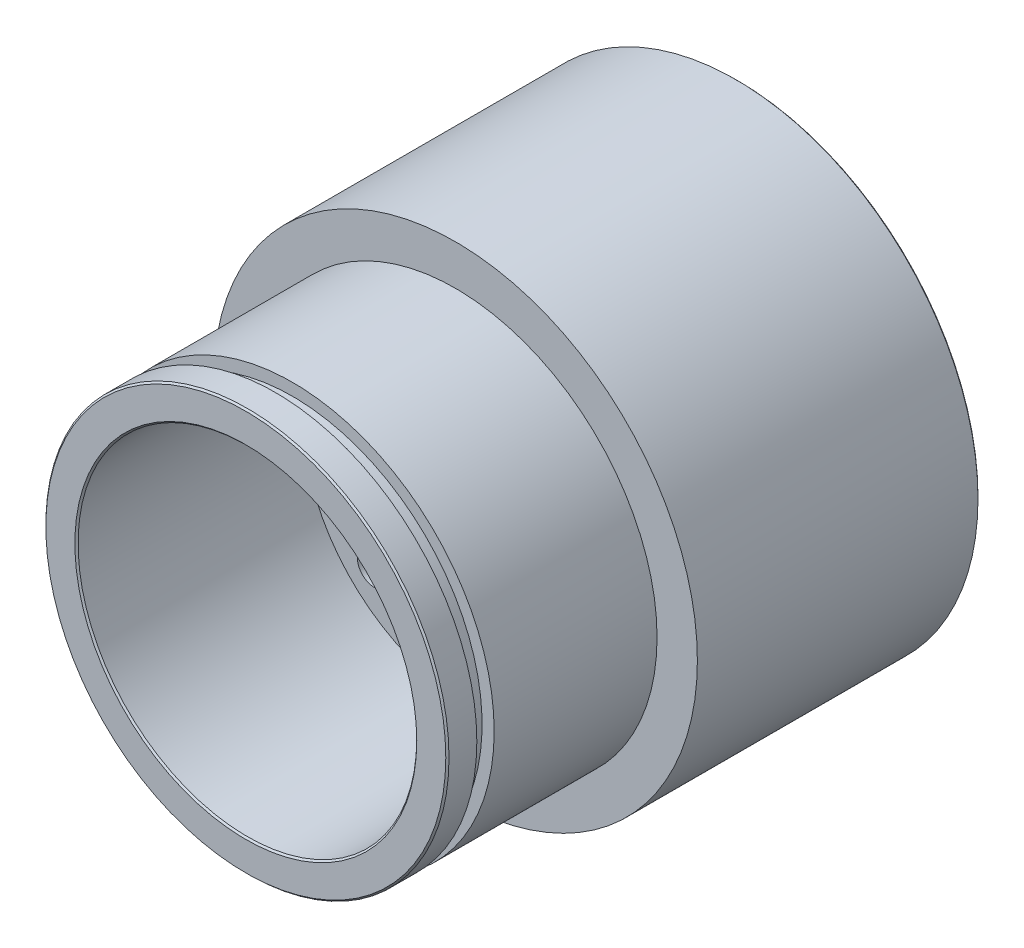
SolidWorks part; units mm, degrees
material "1060 Alloy"
ref_plane "Front Plane" through (0, 0, 0) normal (0, 0, 1) x (1, 0, 0)
ref_plane "Top Plane" through (0, 0, 0) normal (0, 1, 0) x (1, 0, 0)
ref_plane "Right Plane" through (0, 0, 0) normal (1, 0, 0) x (0, 0, -1)
sketch "Sketch1" plane through (0, 0, 0) normal (0, 1, 0) x (1, 0, 0)
  line L0 (0, 0) -> (0, 33) construction
  line L1 (13, 0) -> (21, 0)
  line L2 (21, 0) -> (21, -28)
  line L3 (21, -28) -> (25, -28)
  line L4 (25, -28) -> (25, -2)
  line L6 (30, -2) -> (30, 33)
  line L9 (30, 33) -> (20.5, 33)
  line L10 (20.5, 33) -> (20.5, 4)
  line L11 (20.5, 4) -> (13, 4)
  line L12 (13, 4) -> (13, 0)
  line L13 (25, -2) -> (30, -2)
  dimension "D1" = 26
  dimension "D2" = 50
  dimension "D3" = 4
  dimension "D4" = 4
  dimension "D5" = 41
  dimension "D6" = 6
  dimension "D7" = 35
  dimension "D11" = 60
  dimension "D12" = 26
revolve "Revolve1" add sketch "Sketch1" angle 360 about L0
sketch "Sketch2" plane through (0, 0, 0) normal (0, 1, 0) x (1, 0, 0)
  line L0 (25, -28) -> (25, -2) construction
  line L1 (25, -22.2) -> (23.5, -22.2)
  line L2 (25, -22.2) -> (25, -24.35)
  line L3 (25, -24.35) -> (23.5, -24.35)
  line L4 (23.5, -22.2) -> (23.5, -24.35)
  line L5 (0, -2) -> (0, -28) construction
  line L7 (-25, -28) -> (25, -28) construction
  line L8 (-30, -2) -> (30, -2) construction
  line L10 (-25, -2) -> (25, -2) construction
  dimension "D1" = 2.15
  dimension "D2" = 47
  dimension "D3" = 20.2
revolve "Cut-Revolve1" cut sketch "Sketch2" angle 360 about L5
chamfer "Chamfer1" distance 0.2 angle 45 4 edges at (20.5, 0, -33) (25, 0, 28) (21, 0, 28) (30, 0, -33)
hole_wizard "M4 Clearance Hole1" positions "Sketch3" profile "Sketch4" hole size "M4" standard "ISO" end condition through all
sketch "Sketch3" plane through (0, 0, 0) normal (0, 0, 1) x (1, 0, 0)
  line L0 (-12.0208, 12.0208) -> (0, 0) construction
  line L2 (0, 0) -> (0, 8.8626) construction
  point P0 (-12.0208, 12.0208)
  dimension "D1" = 17
  dimension "D2" = 45
sketch "Sketch4" plane through (-12.0208, 12.0208, 0) normal (1, 0, 0) x (0, -1, 0)
  line L0 (0, 0) -> (0, 33)
  line L1 (0, 33) -> (2.15, 33)
  line L2 (2.15, 33) -> (2.15, 0)
  line L5 (2.15, 0) -> (0, 0)
  line L11 (0, -6.35) -> (0, 107.95) construction
  dimension "Thru Hole Dia." = 4.3
  dimension "Thru Hole Depth" = 33
pattern_circular "CirPattern1" count 4 over 360 about axis through (0, 0, 0) along (0, 0, 1) of "M4 Clearance Hole1"
hole_wizard "M4 Tapped Hole1" positions "Sketch8" profile "Sketch9" tap size "M4" standard "ISO"
sketch "Sketch8" plane through (0, 0, -33) normal (0, 0, -1) x (-1, 0, 0)
  point P0 (0, 25)
  dimension "D1" = 25
cosmetic thread "Hole Thread3" parameters "D1"=10, "D2"=4
sketch "Sketch9" plane through (0, 25, -33) normal (1, 0, 0) x (0, 1, 0)
  line L0 (0, 0) -> (0, 12.9914)
  line L1 (0, 12.9914) -> (1.65, 12)
  line L2 (1.65, 12) -> (1.65, 0)
  line L5 (1.65, 0) -> (0, 0)
  line L10 (0, 12.9914) -> (-1.65, 12) construction
  line L11 (0, -6.35) -> (0, 107.95) construction
  dimension "Tap Drill Dia." = 3.3
  dimension "Tap Drill Depth" = 12
  dimension "Drill Angle" = 118
pattern_circular "CirPattern3" count 6 over 360 about axis through (0, 0, 0) along (0, 0, 1) of "M4 Tapped Hole1" reverse direction yes
move or copy body "Body-Move/Copy1" [suppressed] bodies to move or copy 109
